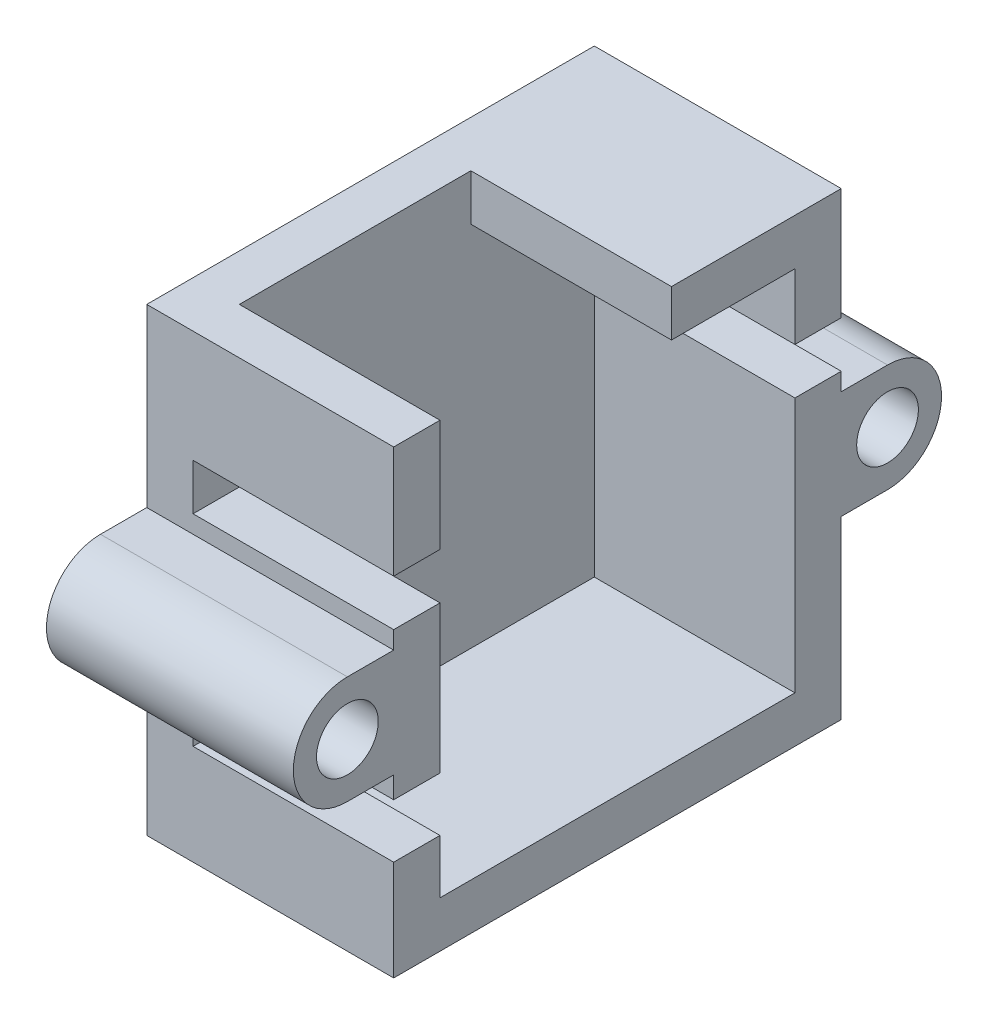
SolidWorks part; units mm, degrees
ref_plane "Front Plane" through (0, 0, 0) normal (0, 0, 1) x (1, 0, 0)
ref_plane "Top Plane" through (0, 0, 0) normal (0, 1, 0) x (1, 0, 0)
ref_plane "Right Plane" through (0, 0, 0) normal (1, 0, 0) x (0, 0, -1)
sketch "Sketch1" plane through (0, 0, 0) normal (1, 0, 0) x (0, 0, -1)
  line L0 (-3, -3) -> (-3, 26.8)
  line L1 (0, 0) -> (23, 0)
  line L2 (0, 0) -> (0, 23.8)
  line L3 (0, 23.8) -> (23, 23.8)
  line L4 (23, 0) -> (23, 23.8)
  line L5 (-3, 26.8) -> (26, 26.8)
  line L6 (26, -3) -> (26, 26.8)
  line L7 (-3, -3) -> (26, -3)
  dimension "D1" = 23.8
  dimension "D2" = 23
  dimension "D3" = 3
extrude "sides" add sketch "Sketch1" along normal blind 13
ref_plane "midplane" through (0, 11.9, 0) normal (0, 1, 0) x (1, 0, 0)
sketch "Sketch2" plane through (0, 0, 0) normal (1, 0, 0) x (0, 0, -1)
  line L0 (-3, 26.8) -> (-3, -3) construction
  line L1 (-3, -3) -> (26, -3) construction
  line L2 (26, -3) -> (26, 26.8) construction
  line L3 (26, 26.8) -> (-3, 26.8) construction
  line L4 (-3, 26.8) -> (-3, -3)
  line L5 (-3, -3) -> (26, -3)
  line L6 (26, -3) -> (26, 26.8)
  line L7 (26, 26.8) -> (-3, 26.8)
extrude "base" add sketch "Sketch2" against normal blind 3
sketch "Sketch3" plane through (0, 0, 0) normal (1, 0, 0) x (0, 0, -1)
  line L1 (-3, 19.55) -> (26, 19.55)
  line L2 (-3, 19.55) -> (-3, 16.55)
  line L3 (-3, 16.55) -> (26, 16.55)
  line L4 (26, 19.55) -> (26, 16.55)
  line L5 (26, -3) -> (26, 26.8) construction
  line L6 (23, 23.8) -> (0, 23.8) construction
  line L7 (-3, 26.8) -> (-3, -3) construction
  dimension "D1" = 4.25
  dimension "D2" = 3
extrude "servo wing slots" cut sketch "Sketch3" along normal up to surface (13 mm away) up to face at (13, 11.9, -11.5)
sketch "Sketch4" plane through (0, 0, 0) normal (1, 0, 0) x (0, 0, -1)
  line L0 (-3, 16.55) -> (-3, -3) construction
  line L1 (-3, 3.5) -> (0, 3.5)
  line L2 (-3, 3.5) -> (-3, 7)
  line L3 (-3, 7) -> (0, 7)
  line L4 (0, 3.5) -> (0, 7)
  line L5 (0, 16.55) -> (0, 0) construction
  line L6 (0, 0) -> (23, 0) construction
  dimension "D1" = 3.5
  dimension "D2" = 3.5
extrude "servo wire slot" cut sketch "Sketch4" along normal up to surface (13 mm away) up to face at (13, 7.525, -11.5)
sketch "Sketch5" plane through (0, 0, 0) normal (1, 0, 0) x (0, 0, -1)
  line L0 (26, 26.8) -> (-3, 26.8) construction
  line L1 (0, 23.8) -> (15, 23.8)
  line L2 (0, 23.8) -> (0, 26.8)
  line L3 (0, 26.8) -> (15, 26.8)
  line L4 (15, 23.8) -> (15, 26.8)
  dimension "D1" = 15
extrude "servo head opening" cut sketch "Sketch5" along normal up to surface (13 mm away) up to face at (13, 22.425, -11.5)
sketch "Sketch6" plane through (0, 0, 0) normal (1, 0, 0) x (0, 0, -1)
  line L0 (-3, 26.8) -> (-3, -3) construction
  line L1 (-3, 26.8) -> (-3, -3) construction
  line L2 (-3, 11.9) -> (26, 11.9) construction
  line L3 (26, -3) -> (26, 16.55) construction
  line L4 (-6, 15.4) -> (-3, 15.4)
  line L5 (-3, 15.4) -> (-3, 8.4)
  line L6 (-3, 8.4) -> (-6, 8.4)
  line L7 (11.5, -3) -> (11.5, 26.8) construction
  line L8 (15, 26.8) -> (0, 26.8) construction
  line L9 (29, 15.4) -> (26, 15.4)
  line L10 (26, 15.4) -> (26, 8.4)
  line L11 (26, 8.4) -> (29, 8.4)
  arc A0 (-6, 15.4) -> (-6, 8.4) centre (-6, 11.9) ccw
  circle A1 centre (-6, 11.9) radius 2
  circle A2 centre (29, 11.9) radius 2
  arc A3 (29, 15.4) -> (29, 8.4) centre (29, 11.9) cw
  point P17 (11.5, 11.9)
  dimension "D2" = 7
  dimension "D3" = 4
  dimension "D1" = 3
extrude "mount" add sketch "Sketch6" along normal up to surface and the other way up to surface contours A0 L6 L5 L4 | L9 L10 L11 A3 | A1 | A2 up to face at (13, 11.775, 1.5) other way up to face at (-3, 11.9, -11.5)
sketch "Sketch7" [suppressed] plane through (0, 0, 0) normal (1, 0, 0) x (0, 0, -1)
  line L0 (-3, -3) -> (26, -3) construction
  line L1 (-8.75, 26) -> (31.75, 26)
  line L2 (-8.75, 26) -> (-8.75, -3)
  line L3 (-8.75, -3) -> (31.75, -3)
  line L4 (31.75, 26) -> (31.75, -3)
  line L5 (15, 26) -> (0, 26) construction
  arc A0 (-6, 14.25) -> (-6, 8.75) centre (-6, 11.5) ccw construction
  arc A1 (29, 8.75) -> (29, 14.25) centre (29, 11.5) ccw construction
extrude "lid cut" [suppressed] cut sketch "Sketch7" along normal up to surface (13 mm away) up to face at (13, 23.3833, -21.3333)
sketch "Sketch9" plane through (0, -3, 0) normal (0, -1, 0) x (1, 0, 0)
  line L0 (13, 3) -> (-3, 3) construction
  line L1 (13, 3) -> (13, -26) construction
  circle A0 centre (6.35, -6.1) radius 2.05
  dimension "D1" = 4.1
  dimension "D2" = 9.1
  dimension "D3" = 6.65
extrude "aligned dummy axle" add sketch "Sketch9" along normal blind 4.5
ref_axis "dummy axle axis" through (6.35, -7.5, -6.1) along (0, 1, 0)
